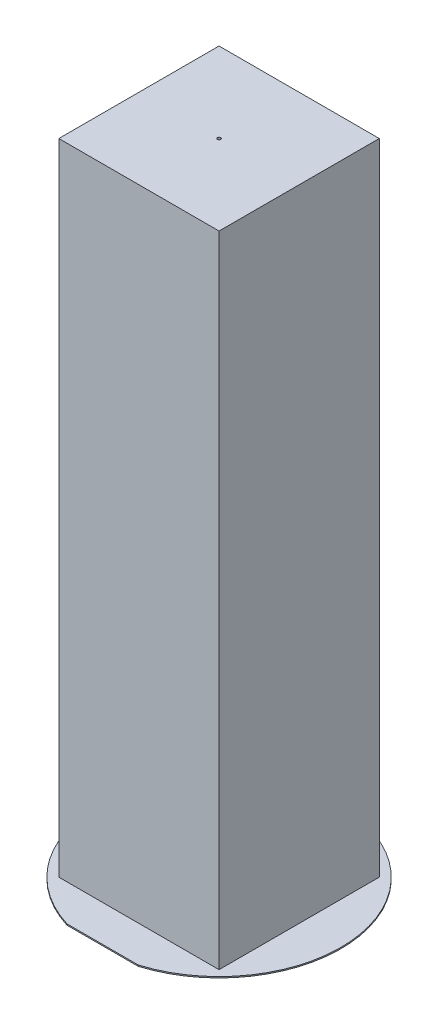
SolidWorks part; units mm, degrees
ref_plane "Front Plane" through (0, 0, 0) normal (0, 0, 1) x (1, 0, 0)
ref_plane "Top Plane" through (0, 0, 0) normal (0, 1, 0) x (1, 0, 0)
ref_plane "Right Plane" through (0, 0, 0) normal (1, 0, 0) x (0, 0, -1)
sketch "Sketch1" plane through (0, 0, 0) normal (0, 1, 0) x (1, 0, 0)
  line L1 (-25, 25) -> (25, 25)
  line L2 (-25, 25) -> (-25, -25)
  line L3 (-25, -25) -> (25, -25)
  line L4 (25, 25) -> (25, -25)
  line L5 (-25, 25) -> (25, -25) construction
  line L6 (-25, -25) -> (25, 25) construction
  circle A0 centre (0, 0) radius 0.5
  point P0 (0, 0)
  dimension "D2" = 1
  dimension "D1" = 50
extrude "Boss-Extrude1" add sketch "Sketch1" along normal blind 0.4
sketch "Sketch2" plane through (0, 0.4, 0) normal (0, 1, 0) x (1, 0, 0)
  line L0 (0, 25) -> (0, -25) construction
  line L1 (25, 25) -> (-25, 25) construction
  line L2 (-25, -25) -> (25, -25) construction
  line L3 (-25, 0) -> (25, 0) construction
  line L4 (-25, 25) -> (-25, -25) construction
  line L5 (25, -25) -> (25, 25) construction
sketch "Sketch3" plane through (0, 0, 0) normal (0, 1, 0) x (1, 0, 0)
  line L0 (-11.11, -36.3396) -> (11.11, -36.3396)
  circle A0 centre (0, 0) radius 38
  point P5 (0, -36.3396)
  dimension "D1" = 76
  dimension "D2" = 22.22
extrude "Boss-Extrude2" add sketch "Sketch3" along normal blind 0.381 contours L0 A0 region at (0, 0, -0.2026)
extrude "Boss-Extrude3" add sketch "Sketch1<2>" along normal blind 200
sketch "Sketch1<2>" plane through (0, 0, 0) normal (0, 1, 0) x (1, 0, 0) same geometry as "Sketch1"
